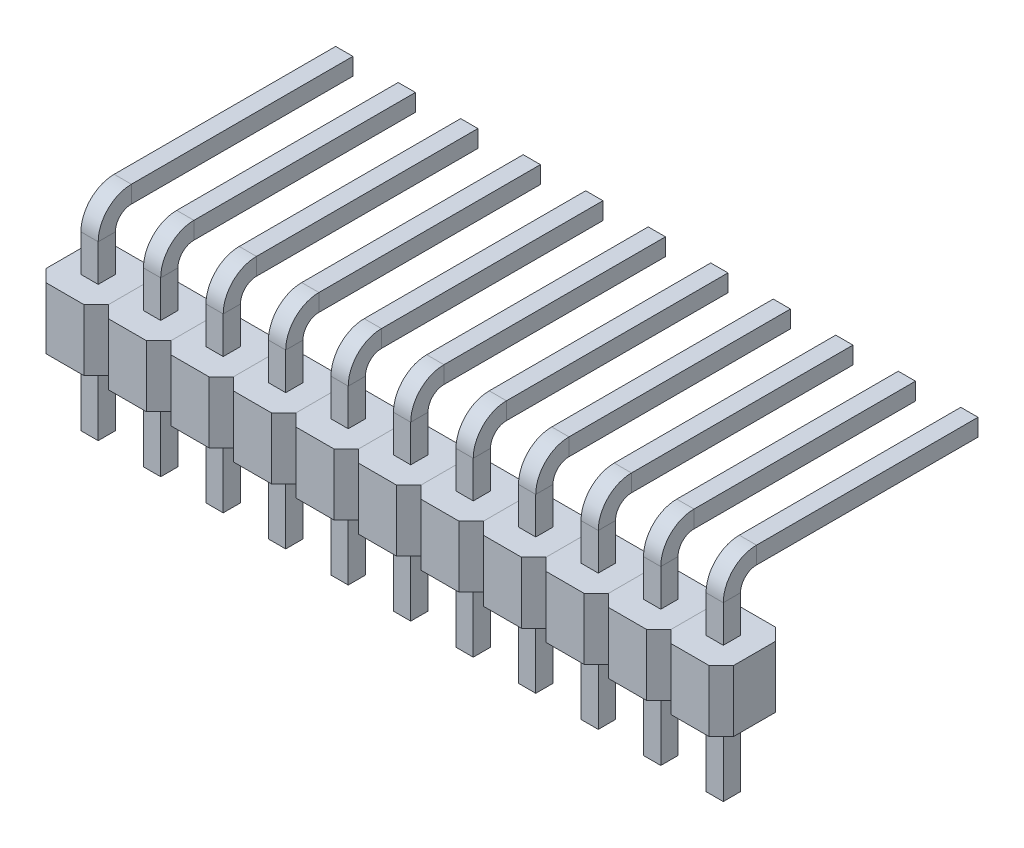
SolidWorks part; units mm, degrees
material "201 Annealed Stainless Steel (SS)"
ref_plane "Front Plane" through (0, 0, 0) normal (0, 0, 1) x (1, 0, 0)
ref_plane "Top Plane" through (0, 0, 0) normal (0, 1, 0) x (1, 0, 0)
ref_plane "Right Plane" through (0, 0, 0) normal (1, 0, 0) x (0, 0, -1)
sketch "Sketch1" plane through (0, 0, 0) normal (0, 1, 0) x (1, 0, 0)
  line L0 (0, 0) -> (2.54, 0)
  line L1 (0, 0) -> (0, -2.7)
  line L3 (2.54, 0) -> (2.54, -2.7)
  line L4 (0.92, -1) -> (1.62, -1)
  line L5 (0.92, -1) -> (0.92, -1.7)
  line L6 (0.92, -1.7) -> (1.62, -1.7)
  line L7 (1.62, -1) -> (1.62, -1.7)
  line L16 (0, -2.7) -> (2.54, -2.7)
  line L17 (0.92, -1) -> (0, 0) construction
  line L18 (1.62, -1.7) -> (2.54, -2.7) construction
  dimension "D2" = 2.54
ref_plane "Plane1" through (1.25, 0, 0) normal (1, 0, 0) x (0, 0, -1)
sketch "Sketch2" plane through (1.25, 0, 0) normal (1, 0, 0) x (0, 0, -1)
  line L0 (-1.35, 4) -> (-1.35, -3)
  line L3 (-0.35, 5) -> (8.65, 5)
  line L4 (0, 0) -> (-2.7, 0) construction
  arc A2 (-1.35, 4) -> (-0.35, 5) centre (-0.35, 4) cw
  point P19 (-1.35, 5)
  dimension "D3" = 1
  dimension "D1" = 8
  dimension "D2" = 1.35
  dimension "D5" = 3
  dimension "D6" = 10
sweep "Sweep3" add profiles "Sketch1" path "Sketch2"
extrude "Boss-Extrude1" add sketch "Sketch1<55>" along normal blind 2.5 separate body contours L3 L16 L1 L0
sketch "Sketch1<55>" plane through (0, 0, 0) normal (0, 1, 0) x (1, 0, 0) same geometry as "Sketch1"
chamfer "Chamfer1" distance 0.5 angle 45 4 edges at (0, 1.25, 2.7) (2.54, 1.25, 2.7) (0, 1.25, 0) (2.54, 1.25, 0)
pattern_linear "LPattern1" count 11 spacing 2.54 along (-1, 0, 0) of bodies 117 101
